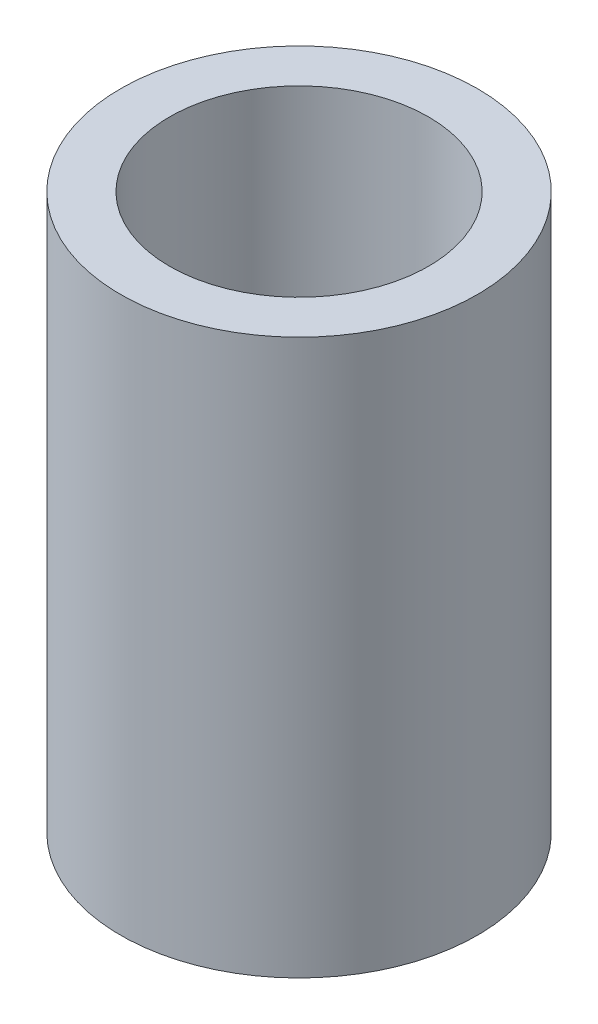
SolidWorks part; units mm, degrees
ref_plane "Front Plane" through (0, 0, 0) normal (0, 0, 1) x (1, 0, 0)
ref_plane "Top Plane" through (0, 0, 0) normal (0, 1, 0) x (1, 0, 0)
ref_plane "Right Plane" through (0, 0, 0) normal (1, 0, 0) x (0, 0, -1)
sketch "Sketch1" plane through (0, 0, 0) normal (0, 1, 0) x (1, 0, 0)
  circle A0 centre (0, 0) radius 6.75
extrude "Boss-Extrude1" add sketch "Sketch1" along normal blind 21
sketch "Sketch2" plane through (0, 21, 0) normal (0, 1, 0) x (1, 0, 0)
  circle A0 centre (0, 0) radius 4.9
extrude "Cut-Extrude1" cut sketch "Sketch2" against normal blind 10
sketch "Sketch3" plane through (0, 0, 0) normal (0, -1, 0) x (1, 0, 0)
  line L1 (-0.8968, -1.2643) -> (1.4032, -0.6583)
  arc A0 (1.4032, -0.6583) -> (-0.8968, -1.2643) centre (0, 0) ccw
  dimension "D1" = 2.3
extrude "Cut-Extrude2" cut sketch "Sketch3" against normal blind 8
